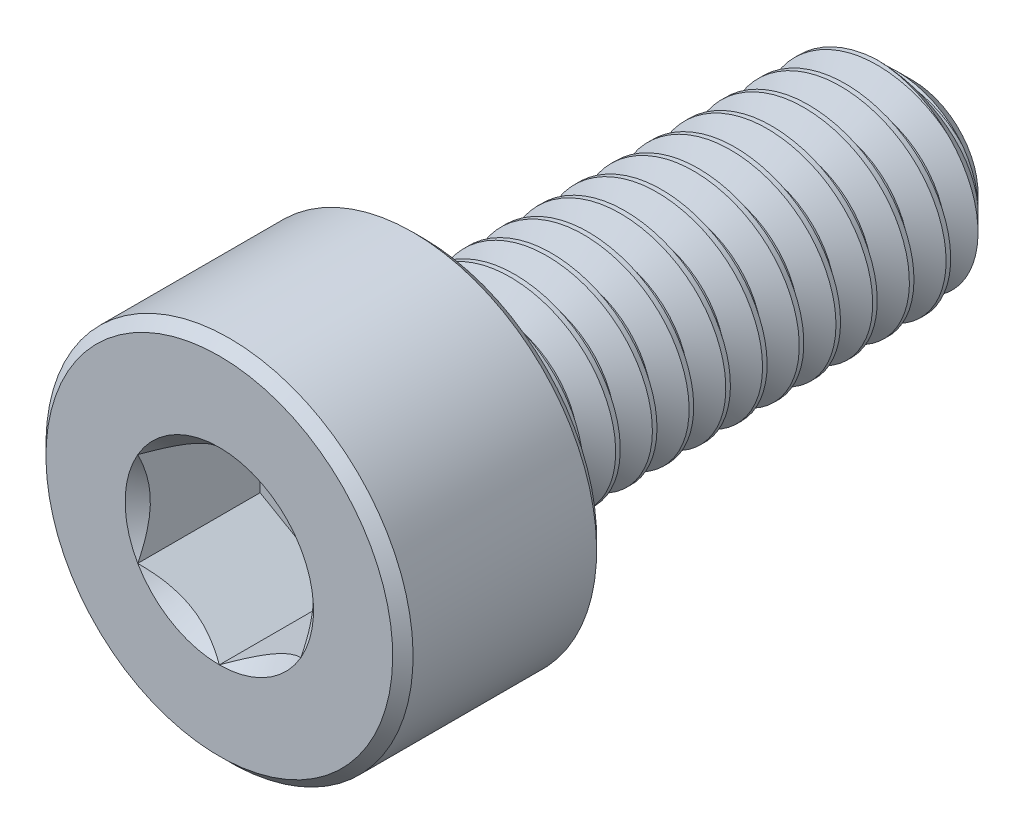
SolidWorks part; units mm, degrees
ref_plane "Front Plane" through (0, 0, 0) normal (0, 0, 1) x (1, 0, 0)
ref_plane "Top Plane" through (0, 0, 0) normal (0, 1, 0) x (1, 0, 0)
ref_plane "Right Plane" through (0, 0, 0) normal (1, 0, 0) x (0, 0, -1)
sketch "Sketch1" plane through (0, 0, 0) normal (1, 0, 0) x (0, 0, -1)
  line L0 (-4.25, 0) -> (4.25, 0) construction
  line L1 (4.25, 0) -> (4.25, 0.8) construction
  line L2 (4.25, 0.8) -> (3.8, 1.25) construction
  line L3 (3.8, 1.25) -> (3.9125, 1.25) construction
  line L4 (3.9125, 1.25) -> (-1.75, 1.25) construction
  line L5 (-1.75, 1.25) -> (-1.75, 2.25) construction
  line L6 (-1.75, 2.25) -> (-4.25, 2.25) construction
  line L7 (-4.25, 2.25) -> (-4.25, 0) construction
  line L8 (4.25, 0.8) -> (4.25, 1.25) construction
  line L9 (4.2219, 1.2987) -> (4.4469, 0.909) construction
  line L10 (4.4469, 0.909) -> (4.6719, 1.2987) construction
  line L11 (4.6719, 1.2987) -> (4.2219, 1.2987) construction
  line L12 (4.4469, 1.2987) -> (4.4469, 1.25) construction
  line L13 (4.4469, 0.909) -> (4.4469, 0.9577) construction
  line L14 (4.4187, 0.9577) -> (4.475, 0.9577) construction
  line L15 (4.25, 1.25) -> (4.6438, 1.25) construction
  line L16 (4.2359, 1.2744) -> (4.6578, 1.2744) construction
  line L17 (4.25, 0) -> (4.25, -1.25) construction
  line L18 (-1.875, 2.25) -> (-1.75, 2.125) construction
  line L19 (-4.125, 2.25) -> (-4.25, 2.125) construction
  line L20 (-1.75, 1.25) -> (-1.75, 0) construction
  line L21 (-1.75, 0.625) -> (0.25, 0.625) construction
  line L22 (0.25, 0.625) -> (2.25, 0.625) construction
  line L23 (2.25, 0.625) -> (4.25, 0.625) construction
  line L24 (0.25, 0.625) -> (0.25, 1.25) construction
  line L25 (0.25, 1.25) -> (0.25, 2.25) construction
  line L26 (2.25, 0.625) -> (2.25, 2.25) construction
  point P0 (-4.25, 1)
  point P3 (3.125, 1.25)
  point P4 (0, 0)
  point P18 (2.25, 1.25)
  point P22 (4.4469, 0.9577)
  point P24 (3.9125, 1.25)
  point P25 (4.4469, 1.25)
  point P28 (4.4469, 1.2744)
  point P29 (3.125, -1.25)
  point P30 (0.25, 1.25)
  point P31 (-3, 2.25)
  point P37 (-2.1875, 2.25)
  point P38 (-4.0625, 2.25)
  point P45 (0.25, 0.625)
  point P46 (2.25, 0.625)
  dimension "D1" = 45
  dimension "D2" = 0.0563
  dimension "D3" = 0.45
  dimension "D7" = 0.125
  dimension "D8" = 0.125
  dimension "D9" = 0.125
  dimension "D10" = 0.0625
  dimension "D11" = 0.3125
  dimension "Drive Size" = 2
  dimension "Head Diameter" = 4.5
  dimension "Head Height" = 2.5
  dimension "Thread Pitch" = 0.45
  dimension "Thread Major Diameter" = 2.5
  dimension "Length" = 6
  dimension "D12" = 0.3375
  dimension "D4" = 1.125
sketch "Sketch2" plane through (0, 0, 0) normal (1, 0, 0) x (0, 0, -1)
  line L0 (-4.25, 0) -> (-4.25, 2.125)
  line L1 (-4.125, 2.25) -> (-1.875, 2.25)
  line L2 (-1.75, 2.125) -> (-1.75, 1.25)
  line L3 (-1.75, 1.25) -> (3.8, 1.25)
  line L4 (3.8, 1.25) -> (4.25, 0.8)
  line L5 (4.25, 0.8) -> (4.25, 0)
  line L6 (-1.875, 2.25) -> (-1.75, 2.125) construction
  line L7 (4.25, 0) -> (-4.25, 0)
  line L8 (-4.125, 2.25) -> (-4.25, 2.125) construction
  line L9 (-1.875, 2.25) -> (-1.75, 2.125)
  line L10 (-4.125, 2.25) -> (-4.25, 2.125)
revolve "Revolve1" add sketch "Sketch2" angle 360 about L7
sketch "Sketch3" plane through (0, 0, 4.25) normal (0, 0, 1) x (1, 0, 0)
  line L1 (1, -0.5774) -> (1, 0.5774)
  line L2 (1, 0.5774) -> (0, 1.1547)
  line L3 (0, 1.1547) -> (-1, 0.5774)
  line L4 (-1, 0.5774) -> (-1, -0.5774)
  line L5 (-1, -0.5774) -> (0, -1.1547)
  line L6 (0, -1.1547) -> (1, -0.5774)
  circle A0 centre (0, 0) radius 1 construction
extrude "Cut-Extrude1" cut sketch "Sketch3" against normal offset from surface (1.5 mm away) 1 up to face at (0, 2.125, 1.75)
sketch "Sketch4" plane through (0, 0, 4.25) normal (0, 0, 1) x (1, 0, 0)
  circle A0 centre (0, 0) radius 1.1547
extrude "Cut-Extrude2" cut sketch "Sketch4" against normal up to vertex (1.25 mm away) draft 45 up to point (0, 2.25, 3)
ref_plane "Plane1" through (0, 0, -3.9125) normal (0, 0, 1) x (1, 0, 0)
split "Split1" bodies to split 106 resulting bodies 107 108 split by face at (0, 2.125, 1.75)
sketch "Sketch6" plane through (0, 0, -4.25) normal (0, 0, -1) x (-1, 0, 0)
  circle A0 centre (0, 0) radius 1.25
curve "Helix/Spiral1" pitch 0.45 height 6.5175 radius 1.25 centre (0, 0, -4.25) axis (0, 0, 1) start towards (0, 1, 0)
sketch "Sketch7" plane through (0, 0, 0) normal (1, 0, 0) x (0, 0, -1)
  line L0 (4.2359, 1.2744) -> (4.6578, 1.2744)
  line L1 (4.6578, 1.2744) -> (4.475, 0.9577)
  line L2 (4.475, 0.9577) -> (4.4187, 0.9577)
  line L3 (4.4187, 0.9577) -> (4.2359, 1.2744)
sweep "Cut-Sweep1" cut profiles "Sketch7" path "Helix/Spiral1" align with end faces yes
sketch "Sketch8" plane through (0, 0, 1.75) normal (0, 0, -1) x (-1, 0, 0)
  circle A0 centre (0, 0) radius 1.25
extrude "Boss-Extrude1" add sketch "Sketch8" along normal through all draft 45
equation "\"D2@Sketch1\" = \"Thread Pitch@Sketch1\" / 8"
equation "\"D3@Sketch1\"= \"Thread Pitch@Sketch1\""
equation "\"D4@Helix/Spiral1\" = \"Thread Pitch@Sketch1\""
equation "\"D7@Sketch1\" = \"Head Height@Sketch1\" * .05"
equation "\"D8@Sketch1\"=\"D7@Sketch1\""
equation "\"D9@Sketch1\"=\"D7@Sketch1\""
equation "\"D10@Sketch1\"=\"D7@Sketch1\"/2"
equation "\"D11@Sketch1\"=\"D10@Sketch1\"*5"
equation "\"D4@Sketch1\"=\"Thread Pitch@Sketch1\"*2.5"
equation "\"D12@Sketch1\"=\"Thread Pitch@Sketch1\"*.75"
